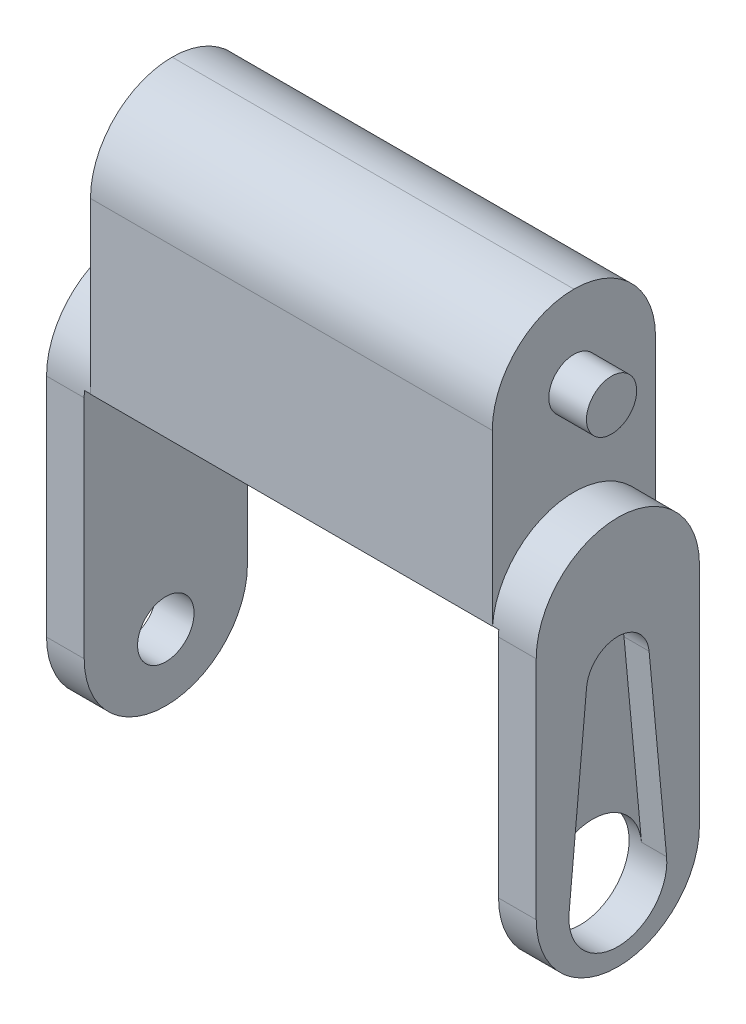
SolidWorks part; units mm, degrees
ref_plane "Plano frontal" through (0, 0, 0) normal (0, 0, 1) x (1, 0, 0)
ref_plane "Plano superior" through (0, 0, 0) normal (0, 1, 0) x (1, 0, 0)
ref_plane "Plano direito" through (0, 0, 0) normal (1, 0, 0) x (0, 0, -1)
sketch "Sketch1" plane through (0, 0, 0) normal (0, 0, 1) x (1, 0, 0)
  line L0 (3, 0) -> (3, 25)
  line L1 (0, 0) -> (3, 0)
  line L2 (0, 0) -> (0, 31)
  line L3 (3.5, 45) -> (35.5, 45)
  line L4 (39, 0) -> (39, 31)
  line L5 (3, 25) -> (36, 25)
  line L6 (36, 25) -> (36, 0)
  line L7 (36, 0) -> (39, 0)
  line L8 (0, 31) -> (3.5, 31)
  line L9 (3.5, 31) -> (3.5, 45)
  line L10 (35.5, 45) -> (35.5, 31)
  line L11 (35.5, 31) -> (39, 31)
  dimension "D1" = 39
  dimension "D2" = 45
  dimension "D3" = 3
  dimension "D4" = 3
  dimension "D5" = 20
  dimension "D6" = 14
  dimension "D7" = 14
  dimension "D8" = 3.5
  dimension "D9" = 32
  dimension "D10" = 3.5
extrude "Boss-Extrude1" add sketch "Sketch1" along normal blind 13
sketch "Sketch2" plane through (0, 0, 0) normal (-1, 0, 0) x (0, 0, 1)
  circle A0 centre (6.5, 5.294) radius 2.25
  dimension "D1" = 4.5
extrude "Cut-Extrude1" cut sketch "Sketch2" against normal blind 3
sketch "Sketch3" plane through (3.5, 0, 0) normal (-1, 0, 0) x (0, 0, 1)
  line L0 (13, 45) -> (0, 45) construction
  circle A0 centre (6.5, 38.5) radius 2
  dimension "D1" = 4
  dimension "D2" = 6.5
extrude "Boss-Extrude3" add sketch "Sketch3" along normal blind 3
sketch "Sketch4" plane through (35.5, 0, 0) normal (1, 0, 0) x (0, 0, -1)
  line L0 (-13, 45) -> (0, 45) construction
  circle A0 centre (-6.5, 38.5) radius 2
  dimension "D1" = 4
  dimension "D2" = 6.5
extrude "Boss-Extrude4" add sketch "Sketch4" along normal blind 3
sketch "Sketch5" plane through (0, 0, 0) normal (-1, 0, 0) x (0, 0, 1)
  line L0 (13, 31) -> (0, 31) construction
  line L1 (13, 31) -> (0, 31) construction
  line L2 (0, 24.5) -> (0, 34.2311)
  line L3 (0, 45) -> (0, 31) construction
  line L4 (0, 34.2311) -> (13, 34.2311)
  line L5 (13, 45) -> (13, 31) construction
  line L6 (13, 34.2311) -> (13, 24.5)
  arc A0 (13, 24.5) -> (0, 24.5) centre (6.5, 24.5) ccw
  point P2 (8.4004, 31)
  dimension "D1" = 13
  dimension "D2" = 6.5
extrude "Cut-Extrude2" cut sketch "Sketch5" along direction (1, 0, 0) on the side against the normal up to surface (3.5 mm away) up to face at (3.5, 38.5, 4.5)
sketch "Sketch6" plane through (39, 0, 0) normal (1, 0, 0) x (0, 0, -1)
  line L1 (-13, 24.5) -> (-13, 34.7123)
  line L2 (-13, 31) -> (-13, 45) construction
  line L3 (-13, 34.7123) -> (0, 34.7123)
  line L4 (0, 31) -> (0, 45) construction
  line L5 (0, 34.7123) -> (0, 24.5)
  line L6 (-13, 31) -> (0, 31) construction
  arc A0 (0, 24.5) -> (-13, 24.5) centre (-6.5, 24.5) ccw
  dimension "D1" = 6.5
extrude "Cut-Extrude3" cut sketch "Sketch6" against normal up to surface (3.5 mm away) up to face at (35.5, 36.5, 6.5)
fillet "Fillet1" radius 6.5 6 edges at (37.5, 0, 13) (37.5, 0, 0) (1.5, 0, 0) (1.5, 0, 13) (19.5, 45, 0) (19.5, 45, 13)
sketch "Sketch7" plane through (36, 0, 0) normal (-1, 0, 0) x (0, 0, 1)
  circle A0 centre (6.5, 5.294) radius 3.9
  dimension "D1" = 7.8
extrude "Cut-Extrude4" cut sketch "Sketch7" against normal through all
sketch "Sketch8" plane through (39, 0, 0) normal (1, 0, 0) x (0, 0, -1)
  line L0 (-6.5, 5.294) -> (-6.5, 20.294) construction
  line L1 (-2.617, 5.658) -> (-4.0109, 20.5273)
  line L2 (-8.9891, 20.5273) -> (-10.383, 5.658)
  arc A0 (-4.0109, 20.5273) -> (-8.9891, 20.5273) centre (-6.5, 20.294) ccw
  circle A1 centre (-6.5, 5.294) radius 3.9 construction
  arc A2 (-10.383, 5.658) -> (-2.617, 5.658) centre (-6.5, 5.294) ccw
  dimension "D1" = 5
  dimension "D2" = 15
extrude "Cut-Extrude5" cut sketch "Sketch8" against normal blind 2
